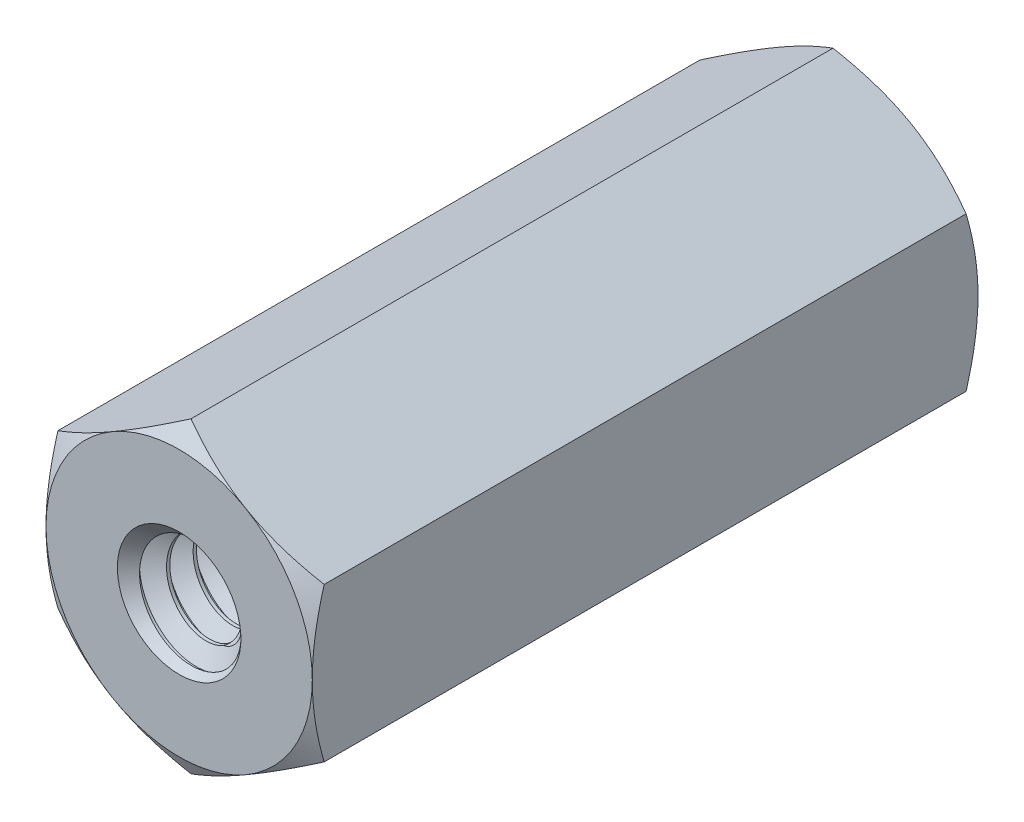
SolidWorks part; units mm, degrees
ref_plane "Front Plane" through (0, 0, 0) normal (0, 0, 1) x (1, 0, 0)
ref_plane "Top Plane" through (0, 0, 0) normal (0, 1, 0) x (1, 0, 0)
ref_plane "Right Plane" through (0, 0, 0) normal (1, 0, 0) x (0, 0, -1)
sketch "Sketch3" plane through (0, 0, 0) normal (1, 0, 0) x (0, 0, -1)
  line L0 (-7.9375, 0) -> (7.9375, 0) construction
  line L1 (0, 3.175) -> (0, -3.175) construction
  line L2 (-7.9375, 1.4224) -> (-7.9375, -1.4224) construction
  point P2 (-7.9375, 0)
  point P3 (7.9375, 0)
  dimension "Length" = 15.875
  dimension "Min Thread Length" = 15.875
  dimension "D1" = 15.875
  dimension "Thread Dia" = 2.8448
  dimension "Hex" = 6.35
sketch "Sketch1" plane through (0, 0, 0) normal (0, 0, 1) x (1, 0, 0)
  line L1 (0, 3.6662) -> (-3.175, 1.8331)
  line L2 (-3.175, 1.8331) -> (-3.175, -1.8331)
  line L3 (-3.175, -1.8331) -> (0, -3.6662)
  line L4 (0, -3.6662) -> (3.175, -1.8331)
  line L5 (3.175, -1.8331) -> (3.175, 1.8331)
  line L6 (3.175, 1.8331) -> (0, 3.6662)
  circle A0 centre (0, 0) radius 3.175 construction
  circle A1 centre (0, 0) radius 1.4224
extrude "Extrude1" add sketch "Sketch1" along normal up to vertex (7.9375 mm away) and the other way up to vertex (7.9375 mm away) up to point (0, 0, 7.9375) other way up to point (0, 0, -7.9375)
sketch "Sketch11" plane through (0, 0, -7.9375) normal (0, 0, -1) x (-1, 0, 0)
  circle A0 centre (0, 0) radius 1.4224 construction
  circle A1 centre (0, 0) radius 1.4224
curve "Helix/Spiral1" pitch 0.635 height 16.51 radius 1.4224 centre (0, 0, -7.9375) axis (0, 0, 1) start towards (0, 1, 0) parameters "Pitch"=0.635
sketch "Sketch12" plane through (0, 0, 0) normal (1, 0, 0) x (0, 0, -1)
  line L0 (8.4931, 1.4224) -> (7.9375, 1.4224)
  line L1 (8.4931, 1.4224) -> (8.255, 1.01)
  line L2 (8.255, 1.01) -> (8.1756, 1.01)
  line L3 (8.1756, 1.01) -> (7.9375, 1.4224)
  line L4 (8.2153, 1.01) -> (8.2153, 1.4224) construction
  line L5 (8.3741, 1.2162) -> (8.0566, 1.2162) construction
  dimension "D1" = 0.0794
  dimension "D2" = 0.3175
  dimension "D3" = 60
sweep "Sweep1" add profiles "Sketch12" path "Helix/Spiral1"
sketch "Sketch6" plane through (0, 0, -7.9375) normal (0, 0, -1) x (-1, 0, 0)
  line L6 (0, 3.6662) -> (-3.175, 1.8331)
  line L7 (-3.175, 1.8331) -> (-3.175, -1.8331)
  line L8 (-3.175, -1.8331) -> (0, -3.6662)
  line L9 (0, -3.6662) -> (3.175, -1.8331)
  line L10 (3.175, -1.8331) -> (3.175, 1.8331)
  line L11 (3.175, 1.8331) -> (0, 3.6662)
  line L12 (0, 3.6662) -> (-3.175, 1.8331)
  line L13 (-3.175, 1.8331) -> (-3.175, -1.8331)
  line L14 (-3.175, -1.8331) -> (0, -3.6662)
  line L15 (0, -3.6662) -> (3.175, -1.8331)
  line L16 (3.175, -1.8331) -> (3.175, 1.8331)
  line L17 (3.175, 1.8331) -> (0, 3.6662)
  dimension "D1" = 0
extrude "Extrude2" cut sketch "Sketch6" along normal through all
sketch "Sketch7" plane through (0, 0, -7.9375) normal (0, 0, -1) x (-1, 0, 0)
  circle A2 centre (0, 0) radius 1.4732
  circle A3 centre (0, 0) radius 1.4732
  dimension "D1" = 0.0508
extrude "Extrude3" cut sketch "Sketch7" against normal through all draft 43
sketch "Sketch8" plane through (0, 0, -7.9375) normal (0, 0, -1) x (-1, 0, 0)
  circle A0 centre (0, 0) radius 3.175 construction
  circle A1 centre (0, 0) radius 3.175
extrude "Extrude4" cut sketch "Sketch8" against normal through all draft 60 flip side to cut
mirror "Mirror1" about plane through (0, 0, 0) normal (0, 0, 1) of "Extrude2", "Extrude3", "Extrude4"
sketch "Sketch9" [suppressed] plane through (0, 0, 0) normal (1, 0, 0) x (0, 0, -1)
  line L1 (-22.225, 3.2258) -> (22.225, 3.2258)
  line L2 (-22.225, 3.2258) -> (-22.225, 0)
  line L3 (-22.225, 0) -> (22.225, 0)
  line L4 (22.225, 3.2258) -> (22.225, 0)
  line L7 (-38.1, 0) -> (38.1, 0) construction
revolve "Revolve" [suppressed] add sketch "Sketch9" angle 360 about L0
sketch "Sketch10" [suppressed] plane through (0, 0, 0) normal (1, 0, 0) x (0, 0, -1)
  line L0 (38.1, 3.175) -> (22.225, 3.175)
  line L1 (-38.1, 3.175) -> (-22.225, 3.175)
  line L2 (22.225, 3.175) -> (22.225, -3.175)
  line L3 (-38.1, -3.2258) -> (-22.225, -3.2258)
  line L4 (-22.225, 3.175) -> (-22.225, -3.2258)
  line L5 (22.225, -3.175) -> (38.1, -3.175)
equation "\"D1@Sketch3\" = \"Min Thread Length@Sketch3\""
equation "\"D3@Helix/Spiral1\" = \"Length@Sketch3\"+\"Pitch@Helix/Spiral1\""
equation "\"D1@Sketch12\" = \"Pitch@Helix/Spiral1\"*.125"
equation "\"D2@Sketch12\" = \"Pitch@Helix/Spiral1\"*.5"
